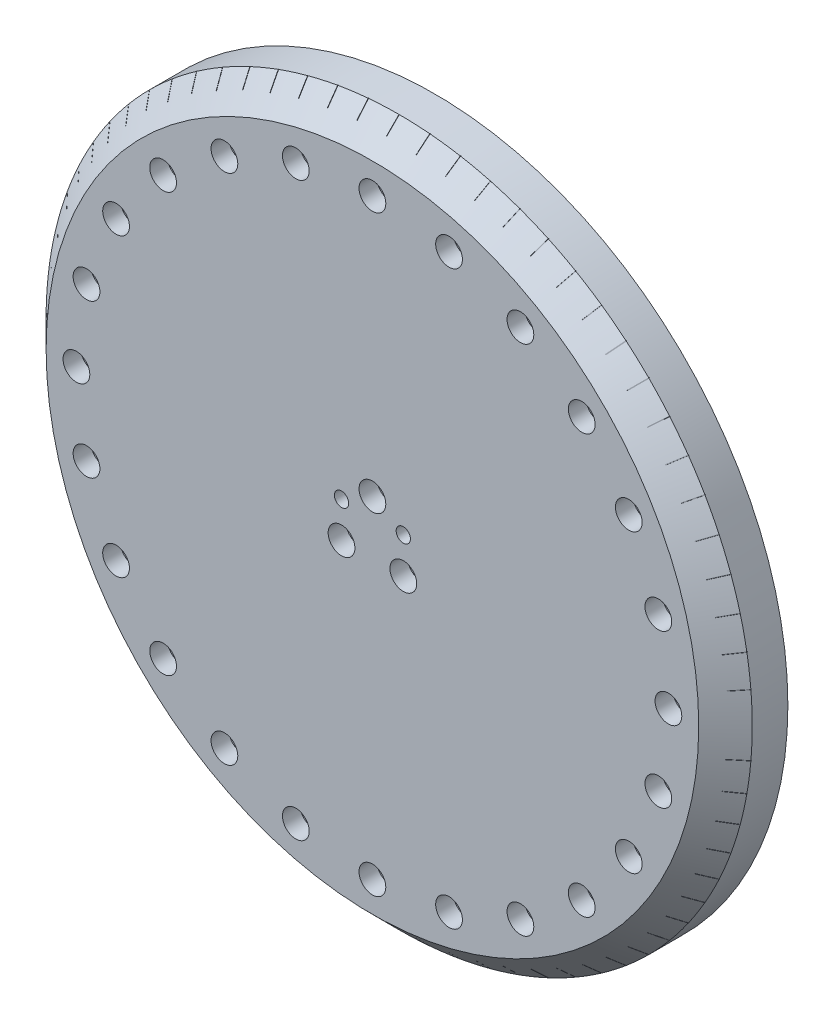
SolidWorks part; units mm, degrees
ref_plane "Plano frontal" through (0, 0, 0) normal (0, 0, 1) x (1, 0, 0)
ref_plane "Plano superior" through (0, 0, 0) normal (0, 1, 0) x (1, 0, 0)
ref_plane "Plano direito" through (0, 0, 0) normal (1, 0, 0) x (0, 0, -1)
sketch "Esboço1" plane through (0, 0, 0) normal (0, 0, 1) x (1, 0, 0)
  circle A0 centre (0, 235) radius 30 construction
  circle A1 centre (0, 235) radius 30 construction
  circle A2 centre (0, 235) radius 198
extrude "Ressalto-extrusão1" add sketch "Esboço1" along normal blind 35
chamfer "Chanfro1" distance 15 angle 45 1 edges at (198, 235, 35)
hole_wizard "Rebaixo para parafuso Allen sextavado de M81" positions "Esboço4" profile "Esboço5" counterbore size "M8" standard "DIN" end condition through all
sketch "Esboço4" plane through (0, 0, 35) normal (0, 0, 1) x (1, 0, 0)
  circle A0 centre (0, 235) radius 183 construction
  point P0 (0, 69)
  dimension "D1" = 166
sketch "Esboço5" plane through (0, 69, 35) normal (1, 0, 0) x (0, -1, 0)
  line L0 (0, 0) -> (0, 35)
  line L1 (0, 35) -> (4.5, 35)
  line L3 (4.5, 35) -> (4.5, 10)
  line L4 (4.5, 10) -> (7.5, 10)
  line L5 (7.5, 10) -> (7.5, 0)
  line L7 (7.5, 0) -> (0, 0)
  line L11 (0, -6.35) -> (0, 107.95) construction
  dimension "Thru Hole Dia." = 9
  dimension "Thru Hole Depth" = 35
  dimension "C'Bore Dia." = 15
  dimension "C'Bore Depth" = 10
ref_axis "Eixo1" through (0, 235, 20) along (0, 0, -1)
pattern_circular "PadrãoCircular1" count 24 over 360 about axis through (0, 235, 20) along (0, 0, -1) of "Rebaixo para parafuso Allen sextavado de M81"
sketch "Esboço7" plane through (0, 0, 0) normal (0, 0, -1) x (-1, 0, 0)
  circle A2 centre (0, 235.0391) radius 30
extrude "Corte-extrusão1" cut sketch "Esboço7" against normal blind 10
hole_wizard "Rebaixo para parafuso Allen sextavado de M82" positions "Esboço8" profile "Esboço9" counterbore size "M8" standard "DIN" end condition through all
sketch "Esboço8" plane through (0, 0, 35) normal (0, 0, 1) x (1, 0, 0)
  line L0 (0, 235) -> (-17.3205, 225) construction
  line L2 (0, 235) -> (17.3205, 225) construction
  line L4 (0, 255) -> (0, 235) construction
  circle A0 centre (0, 235) radius 20 construction
  point P0 (0, 255)
  point P2 (-17.3205, 225)
  point P4 (17.3205, 225)
  dimension "D1" = 40
  dimension "D2" = 120
  dimension "D3" = 120
sketch "Esboço9" plane through (0, 255, 35) normal (1, 0, 0) x (0, -1, 0)
  line L0 (0, 0) -> (0, 35)
  line L1 (0, 35) -> (4.5, 35)
  line L3 (4.5, 35) -> (4.5, 10)
  line L4 (4.5, 10) -> (7.5, 10)
  line L5 (7.5, 10) -> (7.5, 0)
  line L7 (7.5, 0) -> (0, 0)
  line L11 (0, -6.35) -> (0, 107.95) construction
  dimension "Thru Hole Dia." = 9
  dimension "Thru Hole Depth" = 35
  dimension "C'Bore Dia." = 15
  dimension "C'Bore Depth" = 10
hole_wizard "Furos-guia com Ø8.0mm1" positions "Esboço10" profile "Esboço11" hole size "Ø8.0" standard "DIN" end condition through all
sketch "Esboço10" plane through (0, 0, 35) normal (0, 0, 1) x (1, 0, 0)
  circle A0 centre (0, 235) radius 20 construction
  point P0 (-17.3205, 245)
  point P2 (17.3205, 245)
  dimension "D1" = 40
  dimension "D2" = 10
  dimension "D3" = 10
sketch "Esboço11" plane through (-17.3205, 245, 35) normal (1, 0, 0) x (0, -1, 0)
  line L0 (0, 0) -> (0, 35)
  line L1 (0, 35) -> (4, 35)
  line L2 (4, 35) -> (4, 0)
  line L5 (4, 0) -> (0, 0)
  line L11 (0, -6.35) -> (0, 107.95) construction
  dimension "Thru Hole Dia." = 8
  dimension "Thru Hole Depth" = 35
ref_plane "Plano1" through (0, 8.5, -8.5) normal (0, -0.7071, 0.7071) x (-1, 0, 0)
sketch "Esboço15" plane through (0, 8.5, -8.5) normal (0, -0.7071, 0.7071) x (-1, 0, 0)
  line L0 (0, 59.695) -> (0, -59.695) construction
  line L1 (0.1, -50.3051) -> (-0.1, -50.3051)
  line L2 (0.1, -50.3051) -> (0.1, -40.3051)
  line L4 (-0.1, -50.3051) -> (-0.1, -40.3051)
  line L5 (0.1, -40.3051) -> (0.1, -37.3051)
  line L6 (0.1, -37.3051) -> (-0.1, -37.3051)
  line L7 (-0.1, -37.3051) -> (-0.1, -40.3051)
  dimension "D1" = 10
  dimension "D2" = 0.2
  dimension "D3" = 0.1
  dimension "D4" = 3
extrude "Corte-extrusão2" cut sketch "Esboço15" against normal blind 0.2
pattern_circular "PadrãoCircular2" count 72 over 360 about axis through (0, 235, 20) along (0, 0, -1) of "Corte-extrusão2"
sketch "Esboço16" plane through (0, 8.5, -8.5) normal (0, -0.7071, 0.7071) x (-1, 0, 0)
  text T0 "0\r\n" font "Century Gothic" height 5
ref_plane "Plano2" through (109, 0, 109) normal (0.7071, 0, 0.7071) x (0.7071, 0, -0.7071)
sketch "Esboço18" plane through (109, 0, 109) normal (0.7071, 0, 0.7071) x (0.7071, 0, -0.7071)
  text T0 "90" font "Century Gothic" height 5
ref_plane "Plano3" through (-109, 0, 109) normal (-0.7071, 0, 0.7071) x (0.7071, 0, 0.7071)
sketch "Esboço19" plane through (-109, 0, 109) normal (-0.7071, 0, 0.7071) x (0.7071, 0, 0.7071)
  text T0 "-90" font "Century Gothic" height 5
ref_plane "Plano4" through (0, 226.5, 226.5) normal (0, 0.7071, 0.7071) x (1, 0, 0)
sketch "Esboço20" plane through (0, 226.5, 226.5) normal (0, 0.7071, 0.7071) x (1, 0, 0)
  text T0 "180" font "Century Gothic" height 5
